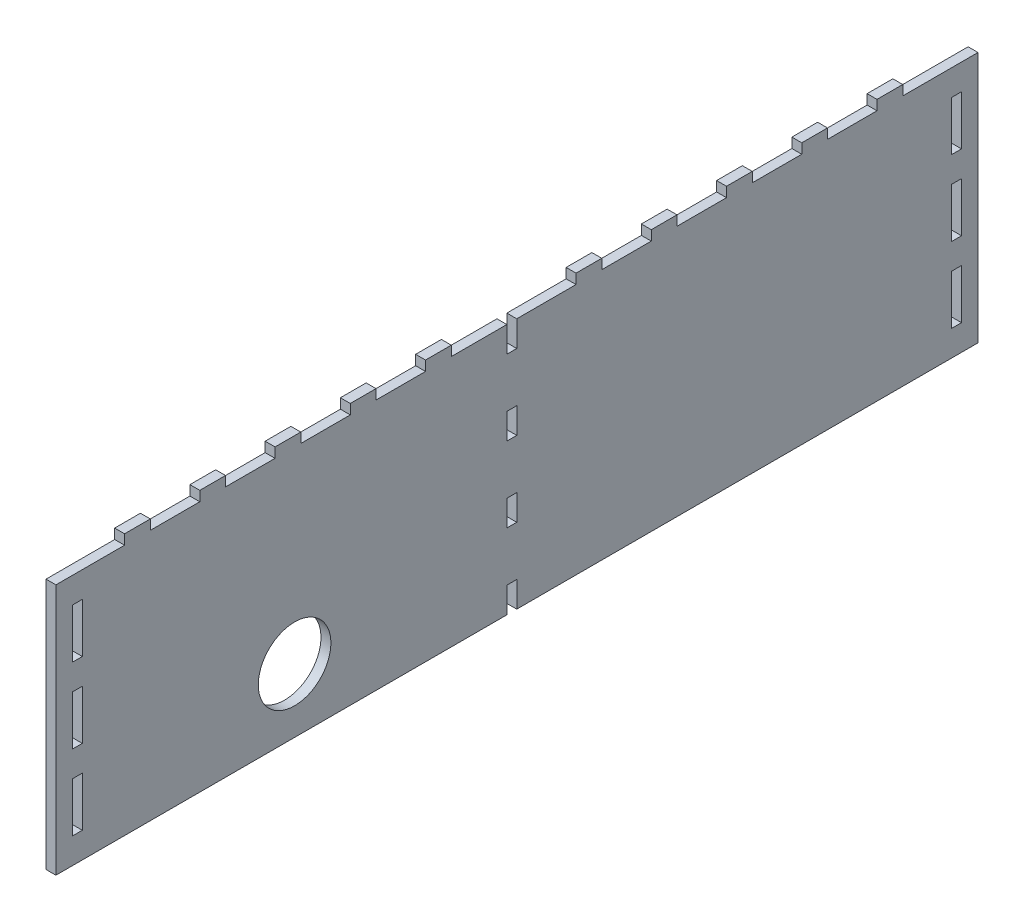
SolidWorks part; units mm, degrees
material "ENPH 253 Hardboard"
ref_plane "Front Plane" through (0, 0, 0) normal (0, 0, 1) x (1, 0, 0)
ref_plane "Top Plane" through (0, 0, 0) normal (0, 1, 0) x (1, 0, 0)
ref_plane "Right Plane" through (0, 0, 0) normal (1, 0, 0) x (0, 0, -1)
sketch "Sketch1" plane through (0, 0, 0) normal (1, 0, 0) x (0, 0, -1)
  line L1 (-139.7, 38.1) -> (139.7, 38.1)
  line L2 (-139.7, 38.1) -> (-139.7, -38.1)
  line L3 (-139.7, -38.1) -> (139.7, -38.1)
  line L4 (139.7, 38.1) -> (139.7, -38.1)
  line L5 (-139.7, 38.1) -> (139.7, -38.1) construction
  line L6 (-139.7, -38.1) -> (139.7, 38.1) construction
  point P0 (0, 0)
  dimension "D1" = 279.4
  dimension "D2" = 76.2
extrude "Boss-Extrude1" add sketch "Sketch1" against normal blind 3 contours L2 L3 L4 L1
sketch "Sketch3" plane through (-3, 0, 0) normal (-1, 0, 0) x (0, 0, 1)
  line L0 (-139.7, 38.1) -> (-139.7, -38.1) construction
  line L1 (139.7, 38.1) -> (139.7, -38.1) construction
  line L2 (139.7, 38.1) -> (-139.7, 38.1) construction
  line L3 (134.7, 30.3) -> (131.7, 30.3)
  line L4 (134.7, 30.3) -> (134.7, 15.3)
  line L5 (134.7, 15.3) -> (131.7, 15.3)
  line L6 (131.7, 30.3) -> (131.7, 15.3)
  line L7 (139.7, 38.1) -> (139.7, -38.1) construction
  circle A0 centre (69.85, 0) radius 50.8 construction
  circle A1 centre (-69.85, 0) radius 50.8 construction
  dimension "D1" = 101.6
  dimension "D2" = 101.6
  dimension "D3" = 69.85
  dimension "D4" = 69.85
  dimension "D5" = 15
  dimension "D6" = 7.8
  dimension "D7" = 5
  dimension "D8" = 3
extrude "Cut-Extrude1" cut sketch "Sketch3" against normal through all
pattern_linear "LPattern1" count 3 spacing 22.8 along (0, -1, 0) of "Cut-Extrude1"
mirror "Mirror1" about plane through (0, 0, 0) normal (0, 0, 1) of "LPattern1"
sketch "Sketch6" plane through (-3, 0, 0) normal (-1, 0, 0) x (0, 0, 1)
  line L0 (139.7, 38.1) -> (-139.7, 38.1) construction
  line L1 (0.06, 38.1) -> (3.06, 38.1)
  line L2 (0.06, 38.1) -> (0.06, 30.3)
  line L3 (0.06, 30.3) -> (3.06, 30.3)
  line L4 (3.06, 38.1) -> (3.06, 30.3)
  dimension "D1" = 136.64
  dimension "D2" = 3
  dimension "D3" = 7.8
extrude "Cut-Extrude2" cut sketch "Sketch6" against normal through all
pattern_linear "LPattern2" count 4 spacing 22.8 along (0, -1, 0) of "Cut-Extrude2"
sketch "Sketch8" plane through (0, 38.1, 0) normal (0, 1, 0) x (1, 0, 0)
  line L0 (0, -139.7) -> (0, -3.06) construction
  line L1 (0, 116.9) -> (-3, 116.9)
  line L2 (0, 116.9) -> (0, 109.1)
  line L3 (0, 109.1) -> (-3, 109.1)
  line L4 (-3, 116.9) -> (-3, 109.1)
  line L5 (-3, -139.7) -> (-3, -3.06) construction
  line L7 (-3, 139.7) -> (0, 139.7) construction
  dimension "D1" = 22.8
  dimension "D2" = 7.8
extrude "Boss-Extrude2" add sketch "Sketch8" along normal blind 3
pattern_linear "LPattern4" count 11 spacing 22.8 along (0, 0, 1) skipping (5, 0) of "Boss-Extrude2"
sketch "Sketch9" plane through (-3, 0, 0) normal (-1, 0, 0) x (0, 0, 1)
  line L0 (139.7, -38.1) -> (3.06, -38.1) construction
  line L1 (3.06, -15.3) -> (3.06, -7.5) construction
  circle A0 centre (67.38, -18.8) radius 11
  dimension "D1" = 22
  dimension "D2" = 19.3
  dimension "D3" = 64.32
extrude "Cut-Extrude3" cut sketch "Sketch9" against normal through all contours A0
equation "\"D4@Sketch3\"=\"D3@Sketch3\""
